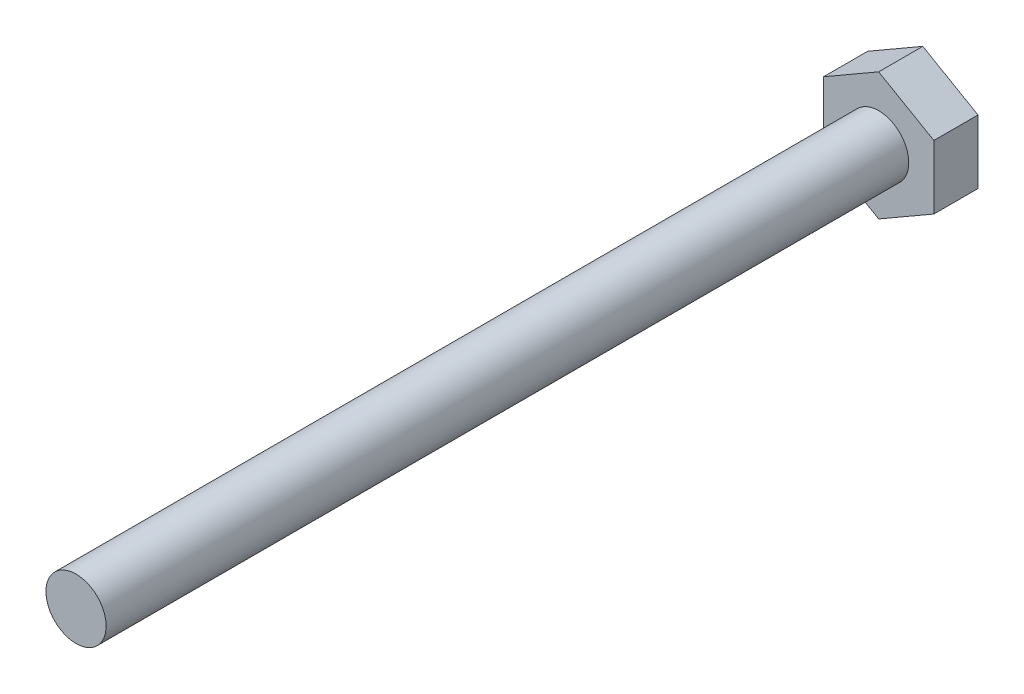
SolidWorks part; units mm, degrees
ref_plane "前视基准面" through (0, 0, 0) normal (0, 0, 1) x (1, 0, 0)
ref_plane "上视基准面" through (0, 0, 0) normal (0, 1, 0) x (1, 0, 0)
ref_plane "右视基准面" through (0, 0, 0) normal (1, 0, 0) x (0, 0, -1)
sketch "草图1" plane through (0, 0, 0) normal (0, 0, 1) x (1, 0, 0)
  line L0 (0, -2.75) -> (0, -3.1754) construction
  line L1 (0, -3.1754) -> (2.75, -1.5877)
  line L2 (2.75, -1.5877) -> (2.75, 1.5877)
  line L3 (2.75, 1.5877) -> (0, 3.1754)
  line L4 (0, 3.1754) -> (-2.75, 1.5877)
  line L5 (-2.75, 1.5877) -> (-2.75, -1.5877)
  line L6 (-2.75, -1.5877) -> (0, -3.1754)
  line L8 (0.249, 0.9029) -> (-0.249, 0.9029)
  line L9 (-0.249, 0.9029) -> (-0.249, 0.249)
  line L10 (-0.249, 0.249) -> (-0.9029, 0.249)
  line L11 (-0.9029, 0.249) -> (-0.9029, -0.249)
  line L12 (0.9029, 0.249) -> (0.9029, -0.249)
  line L13 (0.249, 0.249) -> (0.9029, 0.249)
  line L14 (0.249, 0.9029) -> (0.249, 0.249)
  line L15 (0.249, -0.249) -> (0.9029, -0.249)
  line L16 (0.249, -0.9029) -> (0.249, -0.249)
  line L17 (0.249, -0.9029) -> (-0.249, -0.9029)
  line L18 (-0.249, -0.9029) -> (-0.249, -0.249)
  line L19 (-0.249, -0.249) -> (-0.9029, -0.249)
  circle A0 centre (0, 0) radius 2.75 construction
  circle A1 centre (0, 0) radius 1.5
  point P1 (2.75, 0)
  point P23 (0, 0.9029)
  point P24 (0.9029, 0)
  point P29 (-0.9029, 0)
  dimension "D1" = 5.5
extrude "凸台-拉伸3" add sketch "草图1" along normal blind 2.2 contours L5 L6 L1 L2 L3 L4 A1 region at (-1.333, -2.3088, 0)
extrude "凸台-拉伸4" add sketch "草图1<6>" along normal blind 42.2 contours A1 L18 L19 L11 L10 L9 L8 L14 L13 L12 L15 L16 L17 | L19 L18 L17 L16 L15 L12 L13 L14 L8 L9 L10 L11 region at (0, 0, 0) region at (-1.4576, 0, 0)
sketch "草图1<6>" plane through (0, 0, 0) normal (0, 0, 1) x (1, 0, 0) same geometry as "草图1"
extrude "切除-拉伸1" cut sketch "草图1<9>" against normal blind 1 and the other way blind 1 contours L19 L18 L17 L16 L15 L12 L13 L14 L8 L9 L10 L11 region at (0, 0, 0)
sketch "草图1<9>" plane through (0, 0, 0) normal (0, 0, 1) x (1, 0, 0) same geometry as "草图1"
